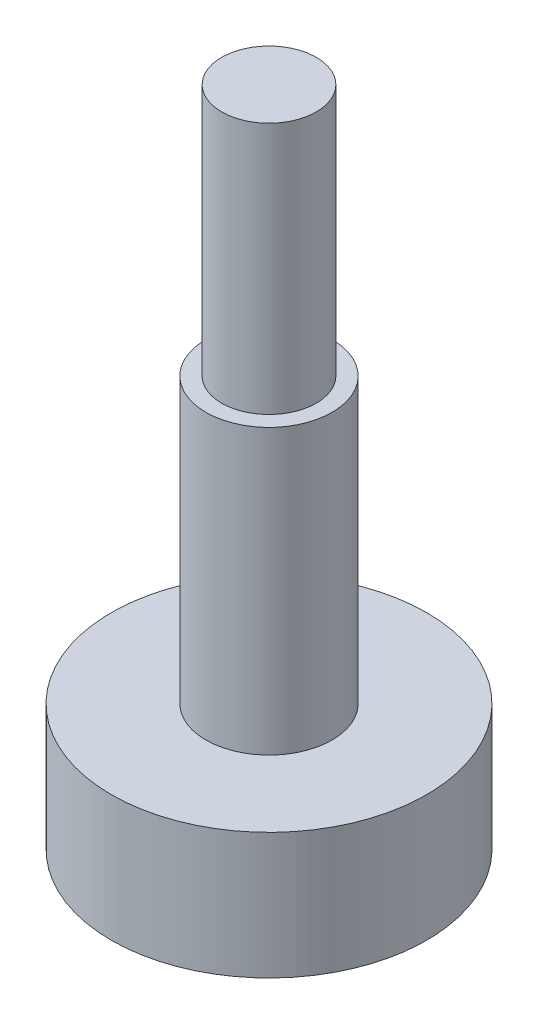
SolidWorks part; units mm, degrees
ref_plane "Front Plane" through (0, 0, 0) normal (0, 0, 1) x (1, 0, 0)
ref_plane "Top Plane" through (0, 0, 0) normal (0, 1, 0) x (1, 0, 0)
ref_plane "Right Plane" through (0, 0, 0) normal (1, 0, 0) x (0, 0, -1)
sketch "Sketch1" plane through (0, 0, 0) normal (0, 0, 1) x (1, 0, 0)
  line L0 (0, 0) -> (5, 0)
  line L1 (3.3, 0) -> (-3.3, 0) construction
  line L2 (5, 0) -> (5, 4)
  line L3 (5, 4) -> (2, 4)
  line L4 (2, 4) -> (2, 13)
  line L5 (2, 13) -> (1.5, 13)
  line L6 (0, -3.3) -> (0, 3.3) construction
  line L7 (0, 21) -> (0, 0)
  line L8 (1.5, 13) -> (1.5, 21)
  line L9 (1.5, 21) -> (0, 21)
  dimension "D1" = 4
  dimension "D2" = 5
  dimension "D3" = 2
  dimension "D4" = 1.5
  dimension "D5" = 17
  dimension "D6" = 8
revolve "Revolve1" add sketch "Sketch1" angle 360 about L7
sketch "Sketch2" plane through (0, 0, 0) normal (0, -1, 0) x (1, 0, 0)
  line L1 (0, -1.7321) -> (1.5, -0.866)
  line L2 (1.5, -0.866) -> (1.5, 0.866)
  line L3 (1.5, 0.866) -> (0, 1.7321)
  line L4 (0, 1.7321) -> (-1.5, 0.866)
  line L5 (-1.5, 0.866) -> (-1.5, -0.866)
  line L6 (-1.5, -0.866) -> (0, -1.7321)
  circle A0 centre (0, 0) radius 1.5 construction
  dimension "D1" = 3
extrude "Cut-Extrude1" cut sketch "Sketch2" against normal blind 2
